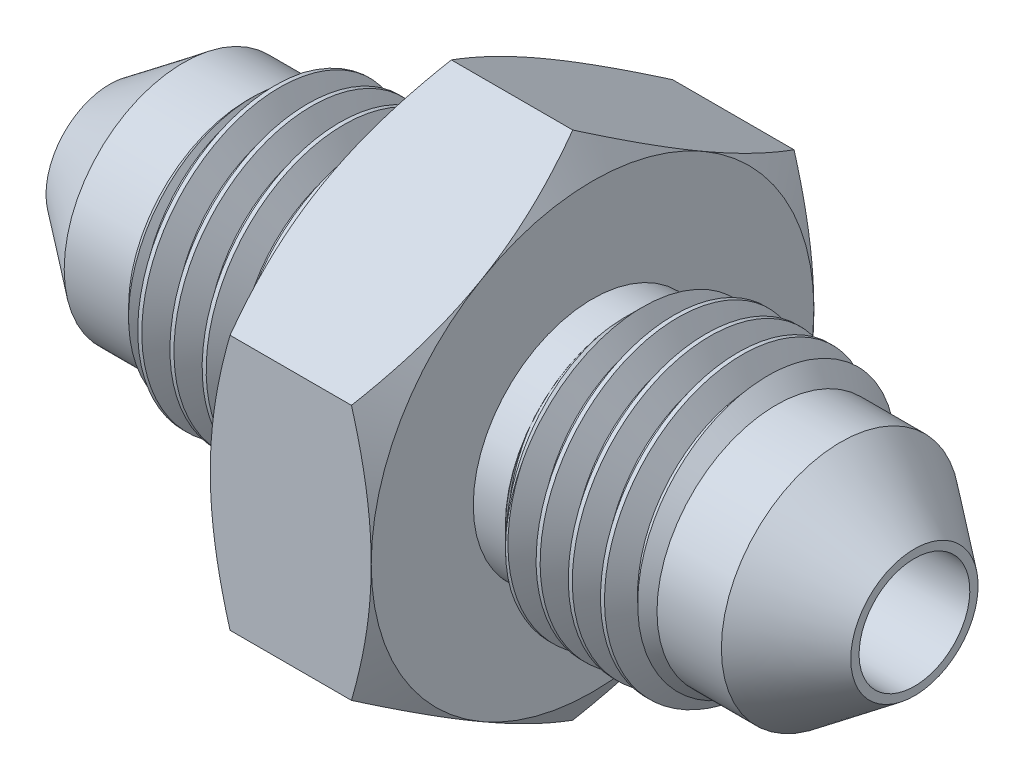
SolidWorks part; units mm, degrees
note: '?' marks a value the reader was unsure of.
ref_plane "Front" through (0, 0, 0) normal (0, 0, 1) x (1, 0, 0)
ref_plane "Top" through (0, 0, 0) normal (0, 1, 0) x (1, 0, 0)
ref_plane "Right" through (0, 0, 0) normal (1, 0, 0) x (0, 0, -1)
sketch "Sketch6" plane through (0, 0, 0) normal (0, 0, 1) x (1, 0, 0)
  line L1 (15.875, 5.5562) -> (15.875, -5.5562) construction
  line L2 (-15.875, 0) -> (15.875, 0)
  line L4 (-15.875, 0) -> (-15.875, 5.5563)
  line L5 (-15.875, 5.5563) -> (15.875, 5.5562)
  line L6 (15.875, 0) -> (15.875, 5.5562)
  point P4 (3.175, 0)
  point P6 (-3.175, 0)
  dimension "Straight Dia" = 11.1125
  dimension "Length" = 31.75
  dimension "L1" = 12.7
revolve "Revolve3" add sketch "Sketch6" angle 360 about L2
sketch "Sketch14" plane through (-15.875, 0, 0) normal (-1, 0, 0) x (0, 0, 1)
  circle A1 centre (0, 0) radius 5.5563
  circle A2 centre (0, 0) radius 5.5563
  dimension "D1" = 0
curve "Helix/Spiral1" pitch 1.27 height 13.97 turns 11 parameters "Pitch"=1.27
sketch "Sketch15" plane through (0, 0, 0) normal (0, 0, 1) x (1, 0, 0)
  line L0 (-16.9863, 5.5563) -> (-15.875, 5.5563)
  line L1 (-15.875, 5.5563) -> (-16.3513, 4.7314)
  line L2 (-16.3513, 4.7314) -> (-16.51, 4.7314)
  line L3 (-16.51, 4.7314) -> (-16.9863, 5.5563)
  line L4 (-16.4306, 4.7314) -> (-16.4306, 5.5563) construction
  line L5 (-16.7481, 5.1438) -> (-16.1131, 5.1438) construction
  dimension "D1" = 60
  dimension "D2" = 0.1588
  dimension "D3" = 0.635
sweep "Cut-Sweep1" cut profiles "Sketch15" path "Helix/Spiral1" align with end faces yes
sketch "Sketch16" plane through (0, 0, 0) normal (1, 0, 0) x (0, 0, -1)
  line L0 (-5.5563, 0) -> (5.5563, 0) construction
  circle A0 centre (0, 0) radius 5.5563 construction
ref_axis "Axis1" through (0, 0, 5.5563) along (0, 0, -1)?
pattern_circular "CirPattern1" count 2 every 180 about axis through (0, 0, 5.5563) along (0, 0, -1) of "Cut-Sweep1"
ref_plane "Plane1" through (-3.175, 0, 0) normal (1, 0, 0) x (0, 0, -1)
sketch "Sketch12" plane through (-3.175, 0, 0) normal (1, 0, 0) x (0, 0, -1)
  line L1 (0, 10.082) -> (-8.7312, 5.041)
  line L2 (-8.7312, 5.041) -> (-8.7312, -5.041)
  line L3 (-8.7312, -5.041) -> (0, -10.082)
  line L4 (0, -10.082) -> (8.7312, -5.041)
  line L5 (8.7312, -5.041) -> (8.7312, 5.041)
  line L6 (8.7312, 5.041) -> (0, 10.082)
  circle A0 centre (0, 0) radius 8.7312 construction
  dimension "Hex" = 17.4625
extrude "Extrude1" add sketch "Sketch12" along normal up to vertex (6.35 mm away) up to point (3.175, 0, 0)
sketch "Sketch7" plane through (0, 0, 0) normal (0, 0, 1) x (1, 0, 0)
  line L0 (-15.875, 0) -> (-15.875, 2.1844)
  line L2 (-15.875, 2.1844) -> (15.875, 2.1844)
  line L4 (15.875, 0) -> (15.875, 5.5562) construction
  line L11 (15.875, 2.1844) -> (15.875, 0)
  line L12 (15.875, 0) -> (-15.875, 0)
  line L13 (-15.875, 2.1844) -> (-15.875, -2.1844) construction
  dimension "ID" = 4.3688
sketch "Sketch10" plane through (0, 0, 0) normal (0, 0, 1) x (1, 0, 0)
  line L0 (-15.875, 5.5563) -> (15.875, 5.5562) construction
  line L1 (-8.8361, -5.5563) -> (-8.8361, 5.5562) construction
  line L2 (-15.875, 0) -> (-15.875, 5.5563) construction
  line L3 (-5.2953, 5.5563) -> (-4.445, 4.706)
  line L4 (-16.9863, 5.5563) -> (-15.875, 5.5563) construction
  line L5 (0, 0) -> (-15.875, 0) construction
  line L6 (5.2953, 5.5563) -> (3.175, 5.5563)
  line L8 (-4.445, 4.706) -> (-3.175, 4.706)
  line L9 (3.175, 4.706) -> (3.175, 5.5563)
  line L11 (0, 0) -> (0, 10.082) construction
  line L12 (3.175, 10.082) -> (-3.175, 10.082) construction
  line L13 (-15.875, 2.5121) -> (-15.875, 5.5563)
  line L14 (-12.9636, 4.706) -> (-15.875, 2.5121)
  line L15 (-10.4236, 4.706) -> (-12.9636, 4.706)
  line L16 (-9.5733, 5.5563) -> (-10.4236, 4.706)
  line L17 (-15.875, 5.5563) -> (-9.5733, 5.5563)
  line L18 (-3.175, 4.706) -> (-3.175, 5.5563)
  line L19 (-5.2953, 5.5563) -> (-3.175, 5.5563)
  line L20 (-3.175, -8.7312) -> (-3.175, 8.7312) construction
  line L21 (15.875, 5.5563) -> (9.5733, 5.5563)
  line L22 (9.5733, 5.5563) -> (10.4236, 4.706)
  line L23 (10.4236, 4.706) -> (12.9636, 4.706)
  line L24 (12.9636, 4.706) -> (15.875, 2.5121)
  line L25 (15.875, 2.5121) -> (15.875, 5.5563)
  line L26 (4.445, 4.706) -> (3.175, 4.706)
  line L27 (5.2953, 5.5563) -> (4.445, 4.706)
  point P9 (-8.8361, -5.5563)
  point P24 (-8.8361, 0)
  dimension "D4" = 37
  dimension "D5" = 1.27
  dimension "D6" = 45
  dimension "D1" = 5.0241
  dimension "D7" = 45
  dimension "D8" = 1.5875
revolve "Cut-Revolve6" cut sketch "Sketch10" angle 360 about L2
revolve "Cut-Revolve5" cut sketch "Sketch7" angle 360 about L12
sketch "Sketch13" plane through (0, 0, 0) normal (0, 0, 1) x (1, 0, 0)
  line L0 (-3.175, 10.082) -> (-3.175, 8.7312)
  line L1 (-3.175, 5.041) -> (-3.175, 10.082) construction
  line L2 (-3.175, 8.7312) -> (-2.3952, 10.082)
  line L3 (-2.3952, 10.082) -> (-3.175, 10.082)
  line L4 (2.3952, 10.082) -> (3.175, 8.7312)
  line L5 (3.175, 10.082) -> (3.175, 5.041) construction
  line L6 (3.175, 8.7312) -> (3.175, 10.082)
  line L7 (3.175, 10.082) -> (2.3952, 10.082)
  dimension "D2" = 30
revolve "Cut-Revolve7" cut sketch "Sketch13" angle 360 about L2
equation "\"D3@Helix/Spiral1\" = \"L1@Sketch6\"+\"Pitch@Helix/Spiral1\""
equation "\"D2@Sketch15\" = \"Pitch@Helix/Spiral1\"*.125"
equation "\"D3@Sketch15\" = \"Pitch@Helix/Spiral1\"*.5"
equation "\"D3@Sketch10\" = \"Pitch@Helix/Spiral1\"*2"
equation "\"D5@Sketch10\" = \"Pitch@Helix/Spiral1\""
equation "\"D1@Sketch10\" = \"ID@Sketch7\"*1.15"
equation "\"D1@Sketch6\" = \"L1@Sketch6\""
equation "\"D8@Sketch10\" = \"Pitch@Helix/Spiral1\"*1.25"
